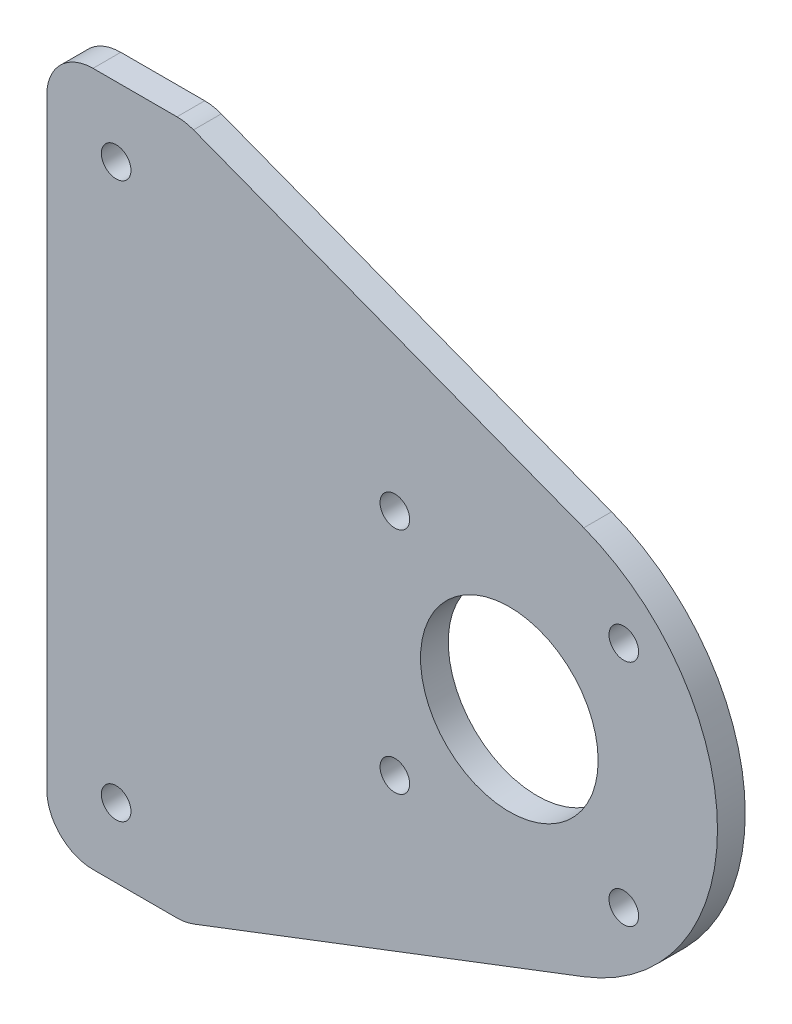
SolidWorks part; units mm, degrees
ref_plane "正面" through (0, 0, 0) normal (0, 0, 1) x (1, 0, 0)
ref_plane "平面" through (0, 0, 0) normal (0, 1, 0) x (1, 0, 0)
ref_plane "右側面" through (0, 0, 0) normal (1, 0, 0) x (0, 0, -1)
sketch "ｽｹｯﾁ2" plane through (0, 0, 0) normal (0, 0, 1) x (1, 0, 0)
  line L0 (12.3744, 12.3744) -> (-12.3744, -12.3744) construction
  line L1 (12.3744, -12.3744) -> (-12.3744, 12.3744) construction
  line L2 (0, 0) -> (-35, 0) construction
  line L3 (-42.5, -30) -> (-42.5, 0) construction
  line L4 (-42.5, 0) -> (-42.5, 30) construction
  line L5 (-50, 37.5) -> (-50, -37.5)
  line L6 (-50, -37.5) -> (-35, -37.5)
  line L7 (-50, 37.5) -> (-35, 37.5)
  line L8 (-35, 37.5) -> (-35, -37.5) construction
  line L9 (-35, 37.5) -> (8.048, 21.0114)
  line L10 (-35, -37.5) -> (8.048, -21.0114)
  line L11 (-50, 0) -> (-35, 0) construction
  line L12 (0, -22.5) -> (-50, -22.5) construction
  line L13 (-50, -22.5) -> (-50, -37.5) construction
  line L14 (0, -30) -> (-50, -30) construction
  line L15 (-50, -37.5) -> (-50, -30) construction
  line L16 (-50, -57.5) -> (-35, -57.5) construction
  line L17 (-35, -57.5) -> (-35, -37.5) construction
  circle A0 centre (0, 0) radius 9.6
  circle A1 centre (-12.3744, 12.3744) radius 1.6
  circle A2 centre (12.3744, 12.3744) radius 1.6
  circle A3 centre (12.3744, -12.3744) radius 1.6
  circle A4 centre (-12.3744, -12.3744) radius 1.6
  circle A5 centre (-42.5, 0) radius 1.6 construction
  circle A6 centre (-42.5, 30) radius 1.6
  circle A7 centre (-42.5, -30) radius 1.6
  arc A8 (8.048, -21.0114) -> (8.048, 21.0114) centre (0, 0) ccw
  circle A9 centre (0, 0) radius 30 construction
  point P6 (0, 0)
  point P9 (0, 0)
  point P29 (-42.5, 0)
  dimension "D1" = 19.2
  dimension "D2" = 3.2
  dimension "D3" = 3.2
  dimension "D4" = 30
  dimension "D5" = 30
  dimension "D8" = 22.5
  dimension "D9" = 15
  dimension "D11" = 7.5
  dimension "D12" = 60
  dimension "D13" = 35
  dimension "D6" = 45
  dimension "D7" = 35
  dimension "D10" = 7.5
  dimension "D15" = 20
  dimension "D16" = 27.5
extrude "ﾎﾞｽ - 押し出し1" add sketch "ｽｹｯﾁ2" along normal blind 3
fillet "ﾌｨﾚｯﾄ3" radius 5 4 edges at (-35, 37.5, 1.5) (-35, -37.5, 1.5) (-50, -37.5, 1.5) (-50, 37.5, 1.5)
